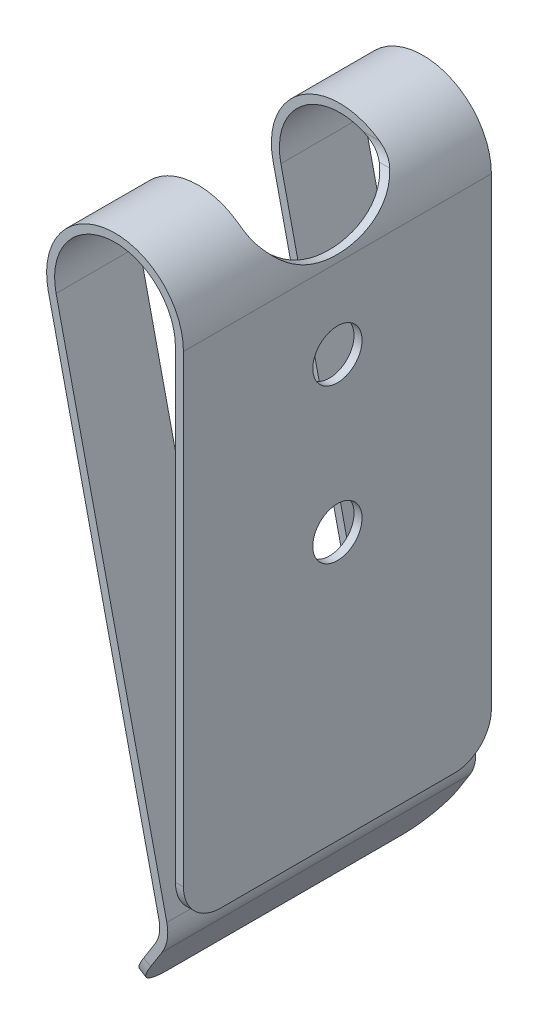
SolidWorks part; units mm, degrees
ref_plane "Front Plane" through (0, 0, 0) normal (0, 0, 1) x (1, 0, 0)
ref_plane "Top Plane" through (0, 0, 0) normal (0, 1, 0) x (1, 0, 0)
ref_plane "Right Plane" through (0, 0, 0) normal (1, 0, 0) x (0, 0, -1)
sketch "Sketch1" plane through (0, 0, 0) normal (0, 0, 1) x (1, 0, 0)
  line L0 (-0.6991, -20.4956) -> (-9.6897, 19.2374)
  line L2 (0, 20.32) -> (0, -20.32)
  line L3 (-1.0941, -22.7947) -> (-3.6221, -26.8013)
  arc A0 (-9.6897, 19.2374) -> (0, 20.32) centre (-4.9053, 20.32) cw
  arc A1 (-0.6991, -20.4956) -> (-1.0941, -22.7947) centre (-3.6719, -21.1683) cw
  point P23 (0, 0)
  point P26 (-0.4204, -21.727)
  dimension "D1" = 12.75
  dimension "D7" = 3.048
  dimension "D2" = 9.75
  dimension "D3" = 42
  dimension "D4" = 40.64
  dimension "D5" = 135
  dimension "D6" = 6
extrude "Extrude-Thin1" add sketch "Sketch1" along normal blind 25 thin thin type one direction wall 0.65
sketch "Sketch2" plane through (-5.7108, -1.2922, 0) normal (-0.9753, -0.2207, 0) x (0, 0, 1)
  line L0 (12.5, 28.4569) -> (12.5, -5.7931) construction
  line L1 (18.25, 28.4569) -> (18.25, -5.7931)
  line L2 (6.75, 28.4569) -> (6.75, -5.7931)
  line L3 (25, -19.8359) -> (0, -19.8359) construction
  line L4 (25, 26.4569) -> (0, 26.4569) construction
  arc A0 (18.25, 28.4569) -> (6.75, 28.4569) centre (12.5, 28.4569) ccw
  arc A1 (6.75, -5.7931) -> (18.25, -5.7931) centre (12.5, -5.7931) ccw
  point P2 (12.5, 11.3319)
  point P9 (12.5, -19.8359)
  point P12 (12.5, -11.5431)
  dimension "D1" = 38
  dimension "D2" = 11.5
  dimension "D3" = 2
extrude "Cut-Extrude1" cut sketch "Sketch2" against normal offset from surface (2.4937 mm away) 2 up to face at (0, 0, 12.5)
sketch "Sketch3" plane through (0, 0, 0) normal (-1, 0, 0) x (0, 0, 1)
  line L0 (18.25, 24.2724) -> (18.25, 25.0551)
  line L6 (18.25, 25.0551) -> (6.75, 25.0551)
  line L7 (6.75, 25.0551) -> (6.75, 24.2724)
  line L8 (18.25, 25.0551) -> (6.75, 25.0551) construction
  line L10 (25, 25.8753) -> (18.25, 25.8753) construction
  arc A2 (6.75, 24.2724) -> (18.25, 24.2724) centre (12.5, 27.4402) ccw
  point P22 (12.5, 25.0551)
  point P24 (12.5, 20.8753)
  dimension "D1" = 5
extrude "Cut-Extrude2" cut sketch "Sketch3" against normal through all both and the other way through all
fillet "Fillet1" radius 2 2 edges at (-1.5007, 24.2724, 18.25) (-1.5007, 24.2724, 6.75)
fillet "Fillet2" radius 3 4 edges at (0.325, -20.32, 0) (0.325, -20.32, 25) (-3.897, -26.6279, 25) (-3.897, -26.6279, 0)
sketch "Sketch4" plane through (0, 0, 0) normal (-1, 0, 0) x (0, 0, 1)
  line L0 (22, -20.32) -> (3, -20.32) construction
  line L1 (6.75, 25.8753) -> (0, 25.8753) construction
  circle A0 centre (12.5, 13.8753) radius 2
  circle A1 centre (12.5, 1.3753) radius 2
  point P7 (12.5, -20.32)
  dimension "D1" = 12
  dimension "D3" = 4
  dimension "D2" = 12.5
extrude "Cut-Extrude3" cut sketch "Sketch4" against normal through all
